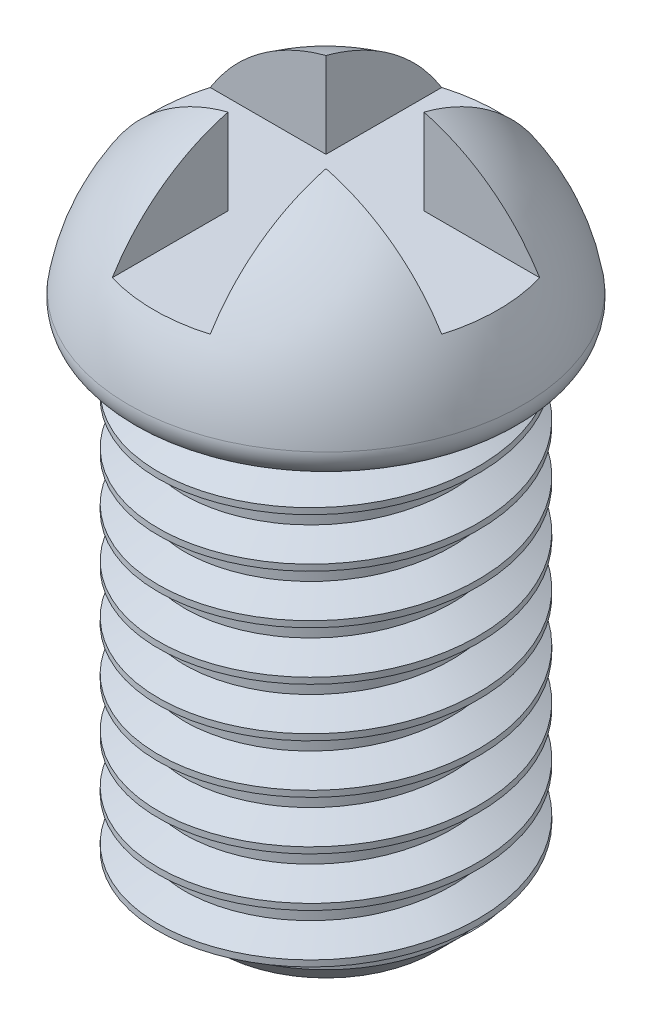
SolidWorks part; units mm, degrees
ref_plane "Front Plane" through (0, 0, 0) normal (0, 0, 1) x (1, 0, 0)
ref_plane "Top Plane" through (0, 0, 0) normal (0, 1, 0) x (1, 0, 0)
ref_plane "Right Plane" through (0, 0, 0) normal (1, 0, 0) x (0, 0, -1)
sketch "Sketch2" plane through (0, 0, 0) normal (0, 1, 0) x (1, 0, 0)
  circle A0 centre (0, 0) radius 1.36
  dimension "D1" = 2.72
extrude "Boss-Extrude1" add sketch "Sketch2" against normal blind 5 contours A0
chamfer "Chamfer1" distance 0.25 angle 45 1 edges at (0, -5, 1.36)
sketch "Sketch5" plane through (0, 0, 0) normal (0, 0, 1) x (1, 0, 0)
  line L0 (0, 0) -> (-2.04, 0)
  line L1 (0, 0) -> (2.04, 0) construction
  line L2 (0, 0) -> (0, 2)
  line L3 (0, 2) -> (-2.04, 2) construction
  arc A0 (0, 2) -> (-2.04, 0) centre (0, -0.0404) ccw
  dimension "D1" = 4.08
  dimension "D2" = 2
revolve "Revolve1" add sketch "Sketch5" angle 360 about L2
thread "Thread1" pitch 0.5 method extrude profile "Thread Profile1" start angle 0, offset 0, length 0, pitch 0.5, diameter 2.72
ref_plane "Plane1" through (-1.36, 0, 0) normal (0, 0, 1) x (-1, 0, 0)
sketch "Thread Profile1" plane through (-1.36, 0, 0) normal (0, 0, 1) x (-1, 0, 0)
  line L0 (0, 0) -> (0, 0.5) construction
  line L1 (0, 0) -> (0.2706, 0.1562)
  line L2 (0.2706, 0.1562) -> (0.2706, 0.2187)
  line L3 (0.2706, 0.2187) -> (0, 0.375)
  line L4 (0.2706, 0.1875) -> (0, 0.1875) construction
  line L11 (0, 0) -> (0, 0.375)
  point P2 (0, 0)
  dimension "Pitch" = 0.5
  dimension "Profile_Angle" = 60
  dimension "Profile_Land" = 0.0625
  dimension "Profile_Height" = 0.2706
fillet "Fillet1" radius 0.25 1 edges at (0, 0, -2.04)
ref_plane "Plane2" through (0, -4.75, 0) normal (0, -1, 0) x (-1, 0, 0)
sketch "Sketch8" plane through (0, -4.75, 0) normal (0, -1, 0) x (-1, 0, 0)
  circle A0 centre (0, 0) radius 1.3587
  circle A1 centre (0, 0) radius 1.7667
  circle A2 centre (0, 0) radius 1.7667 construction
  spline S0 degree 3 poles (-1.36, 0) (-1.36, 0.255) (-1.2817, 0.5305) (-0.9776, 0.984) (-0.7677, 1.1529) (-0.2831, 1.3559) (0.0054, 1.3866) (0.5357, 1.279) (0.7666, 1.155) (1.148, 0.7771) (1.2844, 0.5202) (1.3857, -0.0018) (1.3614, -0.2652) (1.1546, -0.7685) (0.9686, -0.9892) (0.5371, -1.276) (0.2733, -1.36) (0, -1.36) knots 0 0 0 0 0.125 0.125 0.25 0.25 0.375 0.375 0.5 0.5 0.625 0.625 0.75 0.75 0.875 0.875 1 1 1 1 construction
extrude "Cut-Extrude1" cut sketch "Sketch8" along normal through all
ref_plane "Plane3" through (0, 2, 0) normal (0, 1, 0) x (1, 0, 0)
sketch "Sketch9" plane through (0, 2, 0) normal (0, 1, 0) x (1, 0, 0)
  line L1 (-0.5, -2.0134) -> (0.5, -2.0134)
  line L2 (-0.5, -2.0134) -> (-0.5, 2.0134)
  line L3 (-0.5, 2.0134) -> (0.5, 2.0134)
  line L4 (0.5, -2.0134) -> (0.5, 2.0134)
  line L5 (-0.5, -2.0134) -> (0.5, 2.0134) construction
  line L6 (-0.5, 2.0134) -> (0.5, -2.0134) construction
  line L7 (-2.0134, 0.5) -> (2.0134, 0.5)
  line L8 (-2.0134, 0.5) -> (-2.0134, -0.5)
  line L9 (-2.0134, -0.5) -> (2.0134, -0.5)
  line L10 (2.0134, 0.5) -> (2.0134, -0.5)
  line L11 (-2.0134, 0.5) -> (2.0134, -0.5) construction
  line L12 (-2.0134, -0.5) -> (2.0134, 0.5) construction
  circle A0 centre (0, 0) radius 2.0134 construction
  point P0 (0, 0)
  point P8 (0, 0)
  dimension "D1" = 1
  dimension "D2" = 1
extrude "Cut-Extrude2" cut sketch "Sketch9" against normal blind 1 contours L2 L3 L4 L1 | L10 L9 L8 L7
equation "\"inner_diameter\"=2.72"
equation "\"head_diameter\"=4.08"
equation "\"D1@Sketch2\"=\"inner_diameter\""
equation "\"D1@Sketch5\"=\"head_diameter\""
